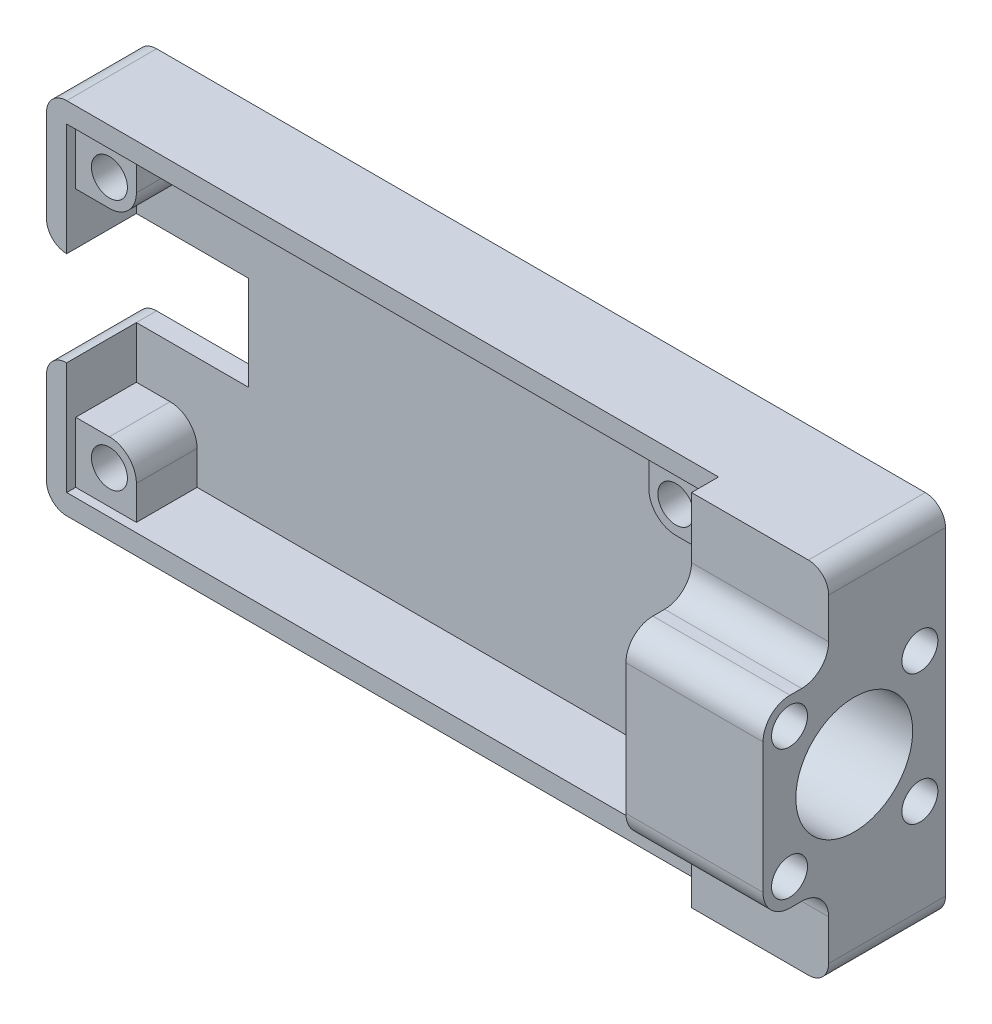
SolidWorks part; units mm, degrees
ref_plane "Front Plane" through (0, 0, 0) normal (0, 0, 1) x (1, 0, 0)
ref_plane "Top Plane" through (0, 0, 0) normal (0, 1, 0) x (1, 0, 0)
ref_plane "Right Plane" through (0, 0, 0) normal (1, 0, 0) x (0, 0, -1)
sketch "Sketch4" plane through (0, 0, 0) normal (0, 0, 1) x (1, 0, 0)
  line L0 (0, 40) -> (0, 25.25)
  line L1 (0, 0) -> (90, 0)
  line L2 (0, 14.75) -> (0, 0)
  line L3 (0, 40) -> (90, 40)
  line L4 (90, 0) -> (90, 40)
  line L5 (14.7, 14.75) -> (14.7, 25.25)
  line L6 (14.7, 25.25) -> (0, 25.25)
  line L7 (14.7, 14.75) -> (0, 14.75)
  line L8 (14.7, 20) -> (90, 20) construction
  line L9 (0, 0) -> (0, 40) construction
  dimension "D1" = 40
  dimension "D2" = 14.7
  dimension "D4" = 10.5
  dimension "D5" = 90
extrude "body" add sketch "Sketch4" along normal blind 10
sketch "Sketch10" plane through (0, 0, 10) normal (0, 0, 1) x (1, 0, 0)
  line L0 (0, 40) -> (0, 0) construction
  line L1 (0, 20) -> (90, 20) construction
  line L2 (90, 0) -> (90, 40) construction
  line L4 (72.75, 2.25) -> (2.25, 2.25)
  line L5 (72.75, 2.25) -> (72.75, 37.75)
  line L6 (72.75, 37.75) -> (2.25, 37.75)
  line L7 (2.25, 2.25) -> (2.25, 37.75)
  line L8 (72.75, 2.25) -> (2.25, 37.75) construction
  line L9 (72.75, 37.75) -> (2.25, 2.25) construction
  point P8 (37.5, 20)
  dimension "D1" = 70.5
  dimension "D2" = 35.5
  dimension "D3" = 2.25
extrude "pcb-recess" cut sketch "Sketch10" against normal offset from surface (7.75 mm away) 2.25 up to face at (26.175, 20, 0)
sketch "Sketch11" plane through (0, 0, 2.25) normal (0, 0, 1) x (1, 0, 0)
  line L0 (2.25, 37.75) -> (2.25, 2.25) construction
  line L1 (2.25, 20) -> (72.75, 20) construction
  line L2 (72.75, 2.25) -> (72.75, 37.75) construction
  line L3 (6, 37.75) -> (6, 2.25) construction
  line L4 (72.75, 37.75) -> (2.25, 37.75) construction
  line L5 (2.25, 2.25) -> (72.75, 2.25) construction
  line L6 (69, 37.75) -> (69, 2.25) construction
  line L7 (72.75, 37.75) -> (2.25, 37.75) construction
  line L8 (2.25, 2.25) -> (72.75, 2.25) construction
  line L9 (2.25, 34) -> (72.75, 34) construction
  line L10 (2.25, 6) -> (72.75, 6) construction
  circle A0 centre (6, 34) radius 3
  circle A1 centre (69, 34) radius 3
  circle A2 centre (69, 6) radius 3
  circle A3 centre (6, 6) radius 3
  point P20 (37.5, 20)
  dimension "D5" = 6
  dimension "D6" = 6
  dimension "D7" = 6
  dimension "D8" = 6
  dimension "D1" = 31.5
  dimension "D2" = 31.5
  dimension "D3" = 14
  dimension "D4" = 14
extrude "pcb-boss" add sketch "Sketch11" along normal offset from surface (6.75 mm away) 1 up to face at (27.875, 20, 10)
fillet "Fillet2" radius 2.25 2 edges at (0, 14.75, 5) (0, 25.25, 5)
sketch "Sketch23" plane through (90, 0, 0) normal (1, 0, 0) x (0, 0, -1)
  line L0 (-10, 0) -> (-10, 40) construction
  line L1 (-10, 30.25) -> (-20.3, 30.25)
  line L2 (-10, 30.25) -> (-10, 9.75)
  line L3 (-10, 9.75) -> (-20.3, 9.75)
  line L4 (-20.3, 30.25) -> (-20.3, 9.75)
  line L5 (-10, 20) -> (-20.3, 20) construction
  dimension "D1" = 20.5
  dimension "D2" = 10.3
extrude "Boss-Extrude2" add sketch "Sketch23" against normal offset from surface (15.25 mm away) 2 up to face at (72.75, 20, 6.125)
sketch "Sketch24" plane through (0, 0, 10) normal (0, 0, 1) x (1, 0, 0)
  line L1 (74.75, 30.25) -> (90, 30.25)
  line L2 (74.75, 30.25) -> (74.75, 40)
  line L3 (74.75, 40) -> (90, 40)
  line L4 (90, 30.25) -> (90, 40)
  line L5 (74.75, 9.75) -> (90, 9.75)
  line L6 (74.75, 9.75) -> (74.75, 0)
  line L7 (74.75, 0) -> (90, 0)
  line L8 (90, 9.75) -> (90, 0)
extrude "Boss-Extrude3" add sketch "Sketch24" along normal blind 3
sketch "Sketch25" plane through (90, 0, 0) normal (1, 0, 0) x (0, 0, -1)
  line L0 (-20.3, 20) -> (0, 20) construction
  line L1 (-20.3, 30.25) -> (-20.3, 9.75) construction
  line L2 (0, 0) -> (0, 40) construction
  circle A0 centre (-10.15, 20) radius 6.5
  dimension "D1" = 13
extrude "Cut-Extrude9" cut sketch "Sketch25" against normal blind 15
sketch "Sketch26" plane through (75, 0, 0) normal (1, 0, 0) x (0, 0, -1)
  line L0 (-10.15, 26.5) -> (-10.15, 13.5)
  circle A0 centre (-10.15, 20) radius 6.5 construction
  circle A1 centre (-10.15, 20) radius 6.5 construction
  arc A2 (-10.15, 26.5) -> (-10.15, 13.5) centre (-10.15, 20) cw
extrude "Cut-Extrude10" cut sketch "Sketch26" against normal up to surface (2.25 mm away) up to face at (72.75, 20, 6.125)
fillet "Fillet7" radius 3 4 edges at (82.375, 9.75, 13) (82.375, 9.75, 20.3) (82.375, 30.25, 20.3) (82.375, 30.25, 13)
fillet "Fillet8" radius 2.25 4 edges at (90, 40, 6.5) (90, 0, 6.5) (0, 0, 5) (0, 40, 5)
sketch "Sketch27" plane through (90, 0, 0) normal (1, 0, 0) x (0, 0, -1)
  line L0 (-25.5029, 27.3) -> (7.3002, 27.3) construction
  line L1 (-25.5029, 12.8) -> (7.3002, 12.8) construction
  line L2 (-17.35, 33.6548) -> (-17.35, 4.2852) construction
  line L3 (-2.85, 33.6548) -> (-2.85, 4.2852) construction
  line L4 (-10.15, 26.5) -> (-10.15, 13.5) construction
  circle A1 centre (-17.35, 27.3) radius 2
  circle A2 centre (-2.85, 27.3) radius 2
  circle A3 centre (-2.85, 12.8) radius 2
  circle A4 centre (-17.35, 12.8) radius 2
  point P10 (-10.15, 20)
  point P19 (-17.65, 27.5)
  point P20 (-2.65, 27.5)
  point P21 (-2.65, 27.5)
  point P22 (0, 0)
  point P23 (-17.65, 27.5)
  point P24 (-17.65, 27.5)
  dimension "D5" = 4
  dimension "D6" = 4
  dimension "D7" = 4
  dimension "D8" = 4
  dimension "D1" = 7.3
  dimension "D2" = 14.5
  dimension "D3" = 7.3
  dimension "D4" = 14.5
extrude "Cut-Extrude11" cut sketch "Sketch27" against normal blind 5.5
sketch "Sketch28" plane through (0, 0, 2.25) normal (0, 0, 1) x (1, 0, 0)
  line L0 (6, 31) -> (2.25, 31)
  line L1 (2.25, 37.75) -> (2.25, 25.25) construction
  line L2 (2.25, 31) -> (2.25, 37.75)
  line L3 (2.25, 37.75) -> (9, 37.75)
  line L4 (2.25, 37.75) -> (72.75, 37.75) construction
  line L5 (9, 37.75) -> (9, 34)
  line L6 (37.5, 37.75) -> (37.5, 2.25) construction
  line L7 (72.75, 2.25) -> (2.25, 2.25) construction
  line L8 (66, 37.75) -> (66, 34)
  line L9 (72.75, 37.75) -> (66, 37.75)
  line L10 (72.75, 31) -> (72.75, 37.75)
  line L11 (69, 31) -> (72.75, 31)
  line L12 (72.75, 20) -> (-5.1979, 20) construction
  line L13 (72.75, 26.4983) -> (72.75, 13.5017) construction
  line L14 (69, 9) -> (72.75, 9)
  line L15 (72.75, 9) -> (72.75, 2.25)
  line L16 (72.75, 2.25) -> (66, 2.25)
  line L17 (66, 2.25) -> (66, 6)
  line L18 (9, 2.25) -> (9, 6)
  line L19 (2.25, 2.25) -> (9, 2.25)
  line L20 (2.25, 9) -> (2.25, 2.25)
  line L21 (6, 9) -> (2.25, 9)
  circle A0 centre (6, 34) radius 3 construction
  circle A1 centre (6, 34) radius 3 construction
  arc A2 (9, 34) -> (6, 31) centre (6, 34) cw
  arc A3 (66, 34) -> (69, 31) centre (69, 34) ccw
  arc A4 (66, 6) -> (69, 9) centre (69, 6) cw
  arc A5 (9, 6) -> (6, 9) centre (6, 6) ccw
  dimension "D1" = 3
extrude "Boss-Extrude4" add sketch "Sketch28" along normal up to surface (6.75 mm away) up to face at (9, 34, 9)
sketch "Sketch12" plane through (0, 0, 9) normal (0, 0, 1) x (1, 0, 0)
  circle A0 centre (6, 34) radius 2
  circle A1 centre (69, 34) radius 2
  circle A2 centre (69, 6) radius 2
  circle A3 centre (6, 6) radius 2
  dimension "D1" = 4
  dimension "D2" = 4
  dimension "D3" = 4
  dimension "D4" = 4
extrude "Cut-Extrude5" cut sketch "Sketch12" against normal blind 4.5
